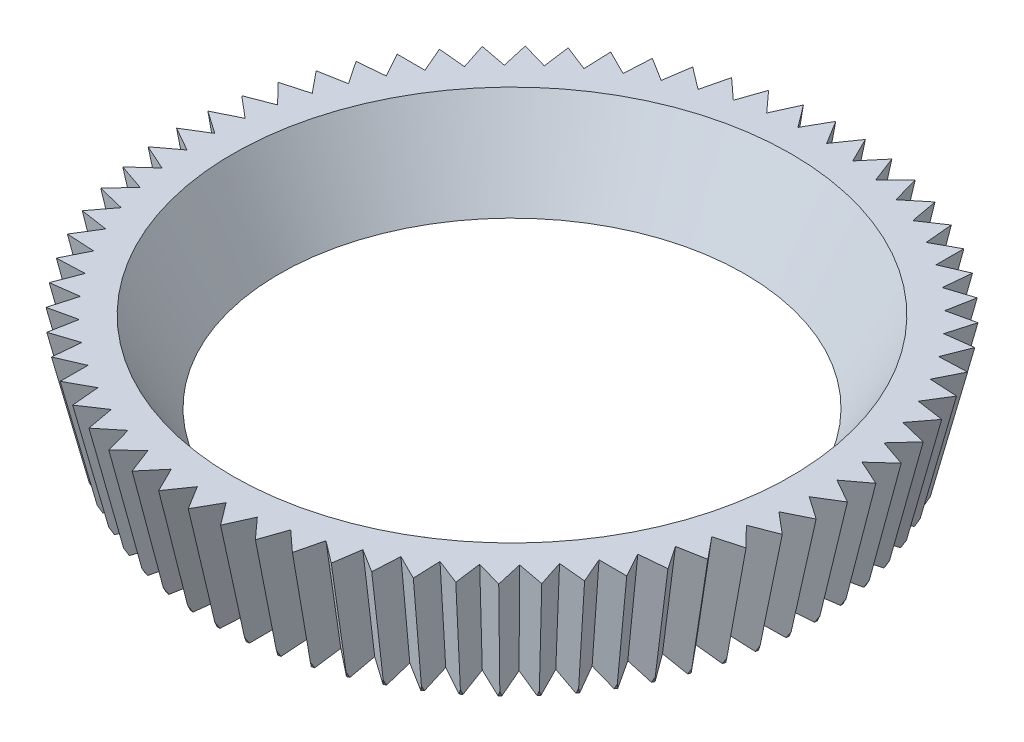
SolidWorks part; units mm, degrees
ref_plane "Front Plane" through (0, 0, 0) normal (0, 0, 1) x (1, 0, 0)
ref_plane "Top Plane" through (0, 0, 0) normal (0, 1, 0) x (1, 0, 0)
ref_plane "Right Plane" through (0, 0, 0) normal (1, 0, 0) x (0, 0, -1)
sketch "Sketch1" plane through (0, 0, 0) normal (0, 0, 1) x (1, 0, 0)
  line L1 (8.0245, 11.8104) -> (9, 13.5)
  line L2 (6.25, 12.8349) -> (7.5, 15)
  line L4 (0, 11.8104) -> (8.0245, 11.8104) construction
  line L5 (0, 11.8104) -> (0, 15) construction
  line L6 (8.0245, 11.8104) -> (6.25, 12.8349)
  line L9 (9, 13.5) -> (9, 15)
  line L10 (9, 15) -> (7.5, 15)
  point P3 (3.8102, 11.8914)
  dimension "D1" = 9
  dimension "D2" = 120
  dimension "D3" = 15
  dimension "D4" = 1.5
  dimension "D5" = 1.5
  dimension "D6" = 2.5
revolve "Revolve1" add sketch "Sketch1" angle 360 about L5
sketch "Sketch2" plane through (0, 15, 0) normal (0, 1, 0) x (1, 0, 0)
  line L0 (0.0739, -8.9997) -> (0.5251, -8.2046)
  line L1 (0.5251, -8.2046) -> (1.0739, -8.9357)
  arc A0 (0.0739, -8.9997) -> (1.0739, -8.9357) centre (0, 0) ccw
  circle A1 centre (0, 0) radius 9 construction
  dimension "D1" = 1
extrude "Cut-Extrude1" cut sketch "Sketch2" against normal through all draft 7 draft outward yes
pattern_circular "CirPattern1" count 68 over 360 about axis through (0, 15, 0) along (0, -1, 0) of "Cut-Extrude1"
